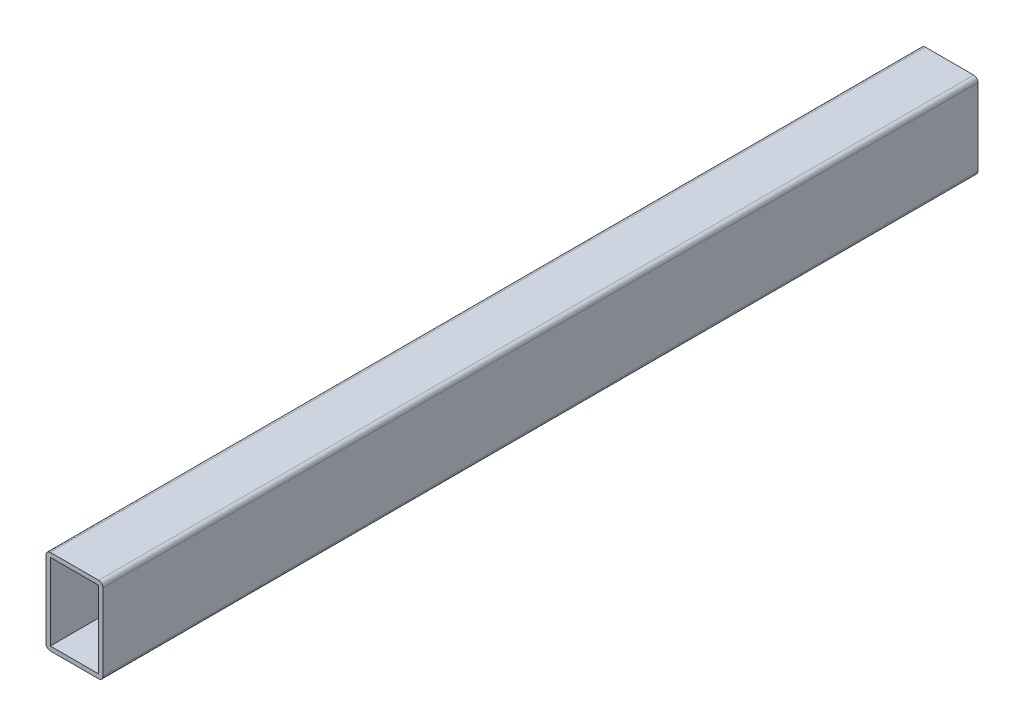
SolidWorks part; units mm, degrees
ref_plane "Front Plane" through (0, 0, 0) normal (0, 0, 1) x (1, 0, 0)
ref_plane "Top Plane" through (0, 0, 0) normal (0, 1, 0) x (1, 0, 0)
ref_plane "Right Plane" through (0, 0, 0) normal (1, 0, 0) x (0, 0, -1)
sketch "Sketch1" plane through (0, 0, 0) normal (0, 0, 1) x (1, 0, 0)
  line L0 (34, 54) -> (-34, 54)
  line L1 (34, -60) -> (-34, -60)
  line L2 (40, -54) -> (40, 54)
  line L3 (34, 60) -> (-34, 60)
  line L4 (-40, -54) -> (-40, 54)
  line L5 (40, -60) -> (-40, 60) construction
  line L6 (40, 60) -> (-40, -60) construction
  line L7 (-34, -54) -> (-34, 54)
  line L8 (34, -54) -> (-34, -54)
  line L9 (34, -54) -> (34, 54)
  arc A0 (-34, -60) -> (-40, -54) centre (-34, -54) cw
  arc A1 (34, -60) -> (40, -54) centre (34, -54) ccw
  arc A2 (40, 54) -> (34, 60) centre (34, 54) ccw
  arc A3 (-34, 60) -> (-40, 54) centre (-34, 54) ccw
  arc A4 (-34, 54) -> (-34, 54) centre (-34, 54) ccw
  arc A5 (-34, -54) -> (-34, -54) centre (-34, -54) cw
  arc A6 (34, -54) -> (34, -54) centre (34, -54) ccw
  arc A7 (34, 54) -> (34, 54) centre (34, 54) ccw
  point P0 (0, 0)
  dimension "D1" = 6
  dimension "D3" = 120
  dimension "D4" = 80
  dimension "D2" = 6
extrude "Boss-Extrude1" add sketch "Sketch1" along normal mid plane 1230
equation "\"M5_tap\"=4.2mm"
equation "\"M5_clearence\"=5.5mm"
equation "\"M6_tap\"=5mm"
equation "\"M6_clearence\"=6.6mm"
equation "\"work_area_width\"=1100mm"
equation "\"work_area_depth\"=900mm"
equation "\"D3@Sketch1\"=\"steel_gantry_width\""
equation "\"D4@Sketch1\"=\"steel_gantry_height\""
equation "\"D1@Sketch1\"=\"steel_gantry_radius\""
equation "\"D2@Sketch1\"=\"steel_gantry_wall_thickness\""
equation "\"D1@Boss-Extrude1\"=\"work_area_width\" + \"steel_sides_height\" + \"steel_rollers_width\""
equation "\"steel_base_width\"=80mm"
equation "\"steel_base_height\"=50mm"
equation "\"steel_base_wall_thickness\"=3mm"
equation "\"steel_base_radius\"=6mm"
equation "\"steel_sides_width\"=180mm"
equation "\"steel_sides_height\"=50mm"
equation "\"steel_sides_wall_thickness\"=5mm"
equation "\"steel_sides_radius\"=6mm"
equation "\"steel_gantry_width\"=120mm"
equation "\"steel_gantry_height\"=80mm"
equation "\"steel_gantry_wall_thickness\"=6mm"
equation "\"steel_gantry_radius\"=6mm"
equation "\"steel_rollers_width\"=80mm"
equation "\"steel_rollers_height\"=50mm"
equation "\"steel_rollers_wall_thickness\"=6mm"
equation "\"steel_rollers_radius\"=6mm"
equation "\"steel_zbox_width\"=400mm"
equation "\"steel_zbox_height\"=90mm"
equation "\"steel_zbox_wall_thickness\"=3mm"
equation "\"steel_zbox_radius\"=6mm"
